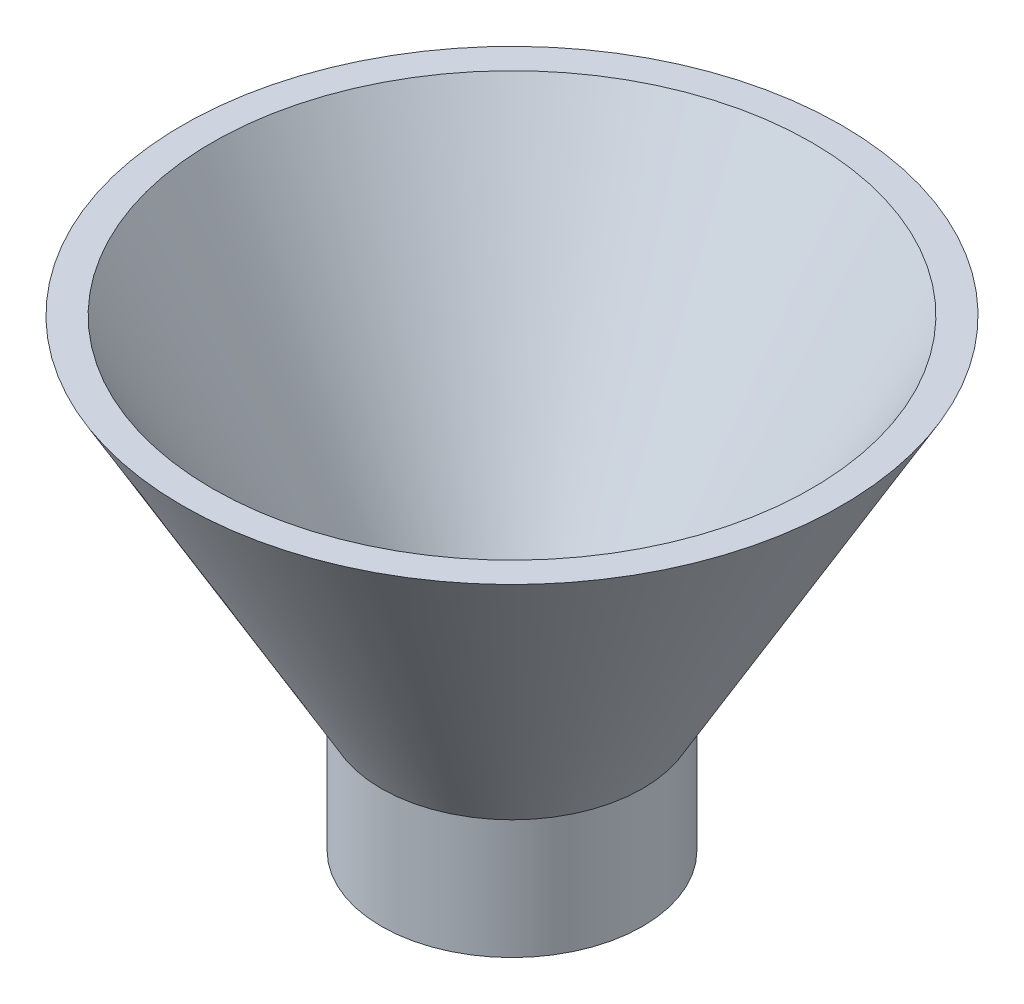
SolidWorks part; units mm, degrees
ref_plane "Front Plane" through (0, 0, 0) normal (0, 0, 1) x (1, 0, 0)
ref_plane "Top Plane" through (0, 0, 0) normal (0, 1, 0) x (1, 0, 0)
ref_plane "Right Plane" through (0, 0, 0) normal (1, 0, 0) x (0, 0, -1)
sketch "Sketch1" plane through (0, 0, 0) normal (0, 1, 0) x (1, 0, 0)
  circle A0 centre (0, 0) radius 13.15
  circle A1 centre (0, 0) radius 10.15
  dimension "D1" = 26.3
  dimension "D2" = 3
extrude "Boss-Extrude1" add sketch "Sketch1" along normal blind 12
sketch "Sketch2" plane through (0, 0, 0) normal (0, 0, 1) x (1, 0, 0)
  line L0 (0, 0) -> (0, 29.4274) construction
  line L1 (-13.15, 12) -> (-33.15, 46.641)
  line L3 (-30.15, 46.641) -> (-10.15, 12)
  line L4 (-10.15, 12) -> (-13.15, 12)
  line L5 (-13.15, 12) -> (-13.15, 42.4912) construction
  line L6 (-33.15, 46.641) -> (-30.15, 46.641)
  dimension "D1" = 40
  dimension "D2" = 30
revolve "Revolve1" add sketch "Sketch2" angle 360 about L0
fillet "Fillet1" radius 10 1 edges at (0, 12, -10.15)
